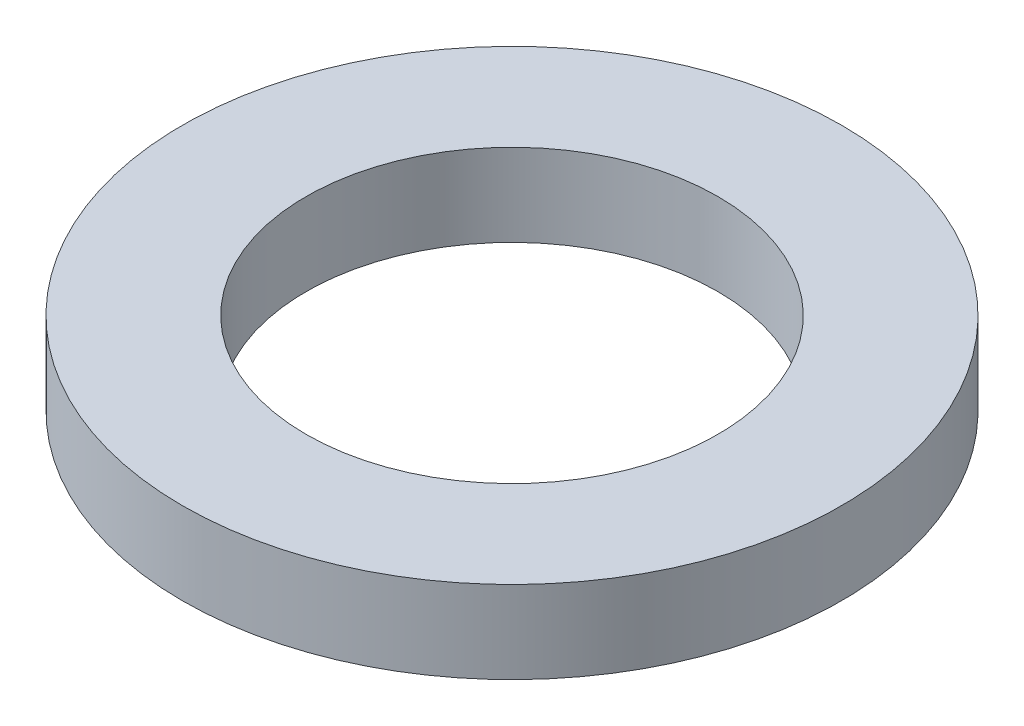
SolidWorks part; units mm, degrees
material "6063-T5"
ref_plane "Спереди" through (0, 0, 0) normal (0, 0, 1) x (1, 0, 0)
ref_plane "Сверху" through (0, 0, 0) normal (0, 1, 0) x (1, 0, 0)
ref_plane "Справа" through (0, 0, 0) normal (1, 0, 0) x (0, 0, -1)
sketch "Эскиз1" plane through (0, 0, 0) normal (0, 1, 0) x (1, 0, 0)
  circle A0 centre (0, 0) radius 4
  circle A1 centre (0, 0) radius 2.5
  dimension "D1" = 8
  dimension "D2" = 5
extrude "Бобышка-Вытянуть1" add sketch "Эскиз1" along normal blind 0.5 and the other way blind 0.5
